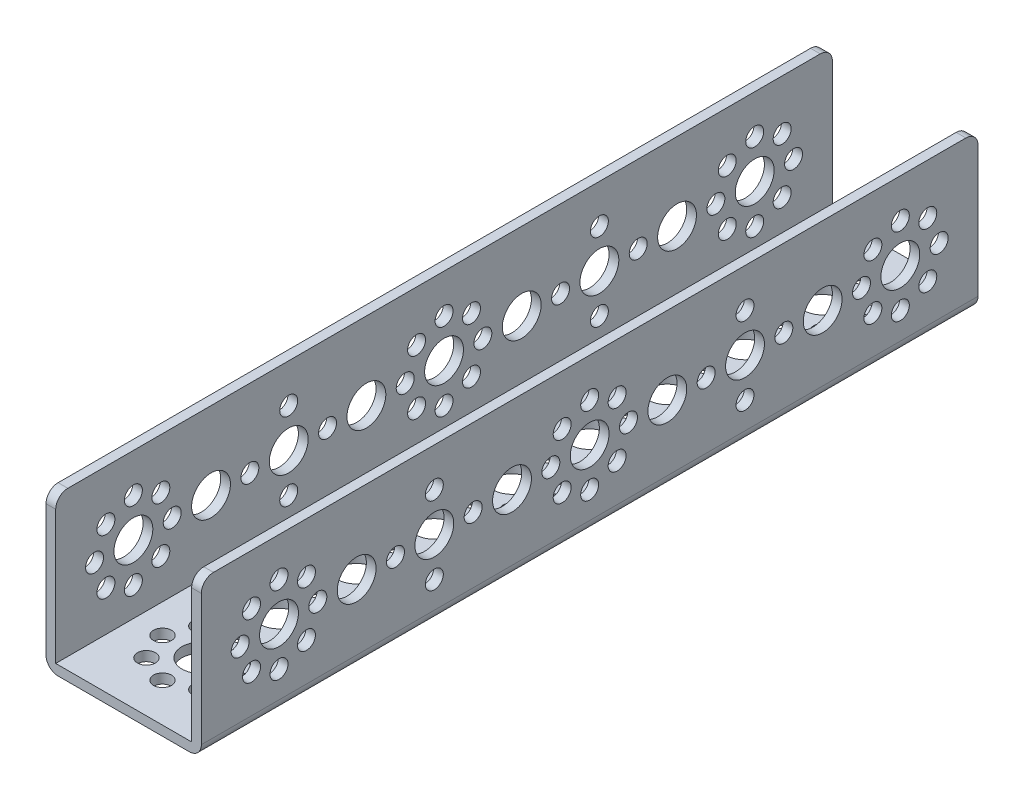
SolidWorks part; units mm, degrees
material "2024 Alloy"
ref_plane "Front Plane" through (0, 0, 0) normal (0, 0, 1) x (1, 0, 0)
ref_plane "Top Plane" through (0, 0, 0) normal (0, 1, 0) x (1, 0, 0)
ref_plane "Right Plane" through (0, 0, 0) normal (1, 0, 0) x (0, 0, -1)
ref_plane "Plane1" through (16, 0, 0) normal (1, 0, 0) x (0, 0, -1)
sketch "Sketch1" plane through (16, 0, 0) normal (1, 0, 0) x (0, 0, -1)
  line L0 (-16, 32) -> (-16, 0)
  line L1 (-16, 0) -> (144, 0)
  line L2 (144, 0) -> (144, 32)
  line L3 (144, 32) -> (-16, 32)
extrude "Boss-Extrude1" add sketch "Sketch1" against normal blind 32
sketch "Sketch2" plane through (0, 0, -144) normal (0, 0, -1) x (-1, 0, 0)
  line L0 (14, 32) -> (-14, 32)
  line L1 (-14, 32) -> (-14, 2)
  line L2 (-14, 2) -> (14, 2)
  line L3 (14, 2) -> (14, 32)
extrude "Cut-Extrude1" cut sketch "Sketch2" against normal through all
hole_wizard "Ø8.0 (8) Diameter Hole1" positions "Sketch4" profile "Sketch3" hole size "Ø8.0" standard "ANSI Metric"
sketch "Sketch4" plane through (-16, 0, 0) normal (-1, 0, 0) x (0, 0, 1)
  point P0 (-64, 16)
  point P1 (-128, 16)
  point P2 (-32, 16)
  point P3 (-96, 16)
  point P4 (-16, 16)
  point P5 (-48, 16)
  point P6 (-80, 16)
  point P7 (-112, 16)
  point P8 (0, 16)
sketch "Sketch3" plane through (-16, 16, -64) normal (0, 1, 0) x (0, 0, 1)
  line L0 (0, 0) -> (0, 2)
  line L1 (0, 2) -> (4, 2)
  line L2 (4, 2) -> (4, 0)
  line L5 (4, 0) -> (0, 0)
  line L11 (0, -6.35) -> (0, 107.95) construction
  dimension "Thru Hole Dia." = 8
  dimension "Thru Hole Depth" = 2
hole_wizard "Ø3.7 (3.7) Diameter Hole1" positions "Sketch6" profile "Sketch5" hole size "Ø3.7" standard "ANSI Metric"
sketch "Sketch6" plane through (-16, 0, 0) normal (-1, 0, 0) x (0, 0, 1)
  point P0 (0, 24)
  point P1 (0, 8)
  point P2 (-8, 16)
  point P3 (8, 16)
  point P4 (-5.6569, 21.6569)
  point P5 (5.6569, 21.6569)
  point P6 (5.6569, 10.3431)
  point P7 (-5.6569, 10.3431)
  point P8 (-64, 24)
  point P9 (-64, 8)
  point P10 (-72, 16)
  point P11 (-56, 16)
  point P12 (-69.6569, 21.6569)
  point P13 (-58.3431, 21.6569)
  point P14 (-58.3431, 10.3431)
  point P15 (-69.6569, 10.3431)
  point P16 (-128, 24)
  point P17 (-128, 8)
  point P18 (-136, 16)
  point P19 (-120, 16)
  point P20 (-133.6569, 21.6569)
  point P21 (-122.3431, 21.6569)
  point P22 (-122.3431, 10.3431)
  point P23 (-133.6569, 10.3431)
  point P24 (-32, 24)
  point P25 (-40, 16)
  point P26 (-32, 8)
  point P27 (-24, 16)
  point P28 (-96, 24)
  point P29 (-104, 16)
  point P30 (-96, 8)
  point P31 (-88, 16)
sketch "Sketch5" plane through (-16, 24, 0) normal (0, 1, 0) x (0, 0, 1)
  line L0 (0, 0) -> (0, 2)
  line L1 (0, 2) -> (1.85, 2)
  line L2 (1.85, 2) -> (1.85, 0)
  line L5 (1.85, 0) -> (0, 0)
  line L11 (0, -6.35) -> (0, 107.95) construction
  dimension "Thru Hole Dia." = 3.7
  dimension "Thru Hole Depth" = 2
hole_wizard "Ø3.7 (3.7) Diameter Hole2" positions "Sketch8" profile "Sketch7" hole size "Ø3.7" standard "ANSI Metric"
sketch "Sketch8" plane through (0, 0, 0) normal (0, -1, 0) x (-1, 0, 0)
  point P0 (8, 0)
  point P1 (5.6569, 5.6569)
  point P2 (0, 8)
  point P3 (-5.6569, 5.6569)
  point P4 (-8, 0)
  point P5 (-5.6569, -5.6569)
  point P6 (0, -8)
  point P7 (5.6569, -5.6569)
  point P8 (8, 64)
  point P9 (5.6569, 69.6569)
  point P10 (0, 72)
  point P11 (-5.6569, 69.6569)
  point P12 (-8, 64)
  point P13 (-5.6569, 58.3431)
  point P14 (0, 56)
  point P15 (5.6569, 58.3431)
  point P16 (8, 128)
  point P17 (5.6569, 133.6569)
  point P18 (0, 136)
  point P19 (-5.6569, 133.6569)
  point P20 (-8, 128)
  point P21 (-5.6569, 122.3431)
  point P22 (0, 120)
  point P23 (5.6569, 122.3431)
  point P24 (8, 32)
  point P25 (0, 40)
  point P26 (-8, 32)
  point P27 (0, 24)
  point P28 (8, 96)
  point P29 (0, 104)
  point P30 (-8, 96)
  point P31 (0, 88)
sketch "Sketch7" plane through (-8, 0, 0) normal (1, 0, 0) x (0, 0, -1)
  line L0 (0, 0) -> (0, 32)
  line L1 (0, 32) -> (1.85, 32)
  line L2 (1.85, 32) -> (1.85, 0)
  line L5 (1.85, 0) -> (0, 0)
  line L11 (0, -6.35) -> (0, 107.95) construction
  dimension "Thru Hole Dia." = 3.7
  dimension "Thru Hole Depth" = 32
hole_wizard "Ø8.0 (8) Diameter Hole2" positions "Sketch10" profile "Sketch9" hole size "Ø8.0" standard "ANSI Metric"
sketch "Sketch10" plane through (0, 0, 0) normal (0, -1, 0) x (-1, 0, 0)
  point P0 (0, 0)
  point P1 (0, 64)
  point P2 (0, 128)
  point P3 (0, 32)
  point P4 (0, 96)
  point P5 (0, 16)
  point P6 (0, 48)
  point P7 (0, 80)
  point P8 (0, 112)
sketch "Sketch9" plane through (0, 0, 0) normal (1, 0, 0) x (0, 0, -1)
  line L0 (0, 0) -> (0, 32)
  line L1 (0, 32) -> (4, 32)
  line L2 (4, 32) -> (4, 0)
  line L5 (4, 0) -> (0, 0)
  line L11 (0, -6.35) -> (0, 107.95) construction
  dimension "Thru Hole Dia." = 8
  dimension "Thru Hole Depth" = 32
hole_wizard "Ø8.0 (8) Diameter Hole3" positions "Sketch12" profile "Sketch11" hole size "Ø8.0" standard "ANSI Metric"
sketch "Sketch12" plane through (14, 0, 0) normal (-1, 0, 0) x (0, 0, 1)
  point P0 (-32, 16)
sketch "Sketch11" plane through (14, 16, -32) normal (0, 1, 0) x (0, 0, 1)
  line L0 (0, 0) -> (0, 2)
  line L1 (0, 2) -> (4, 2)
  line L2 (4, 2) -> (4, 0)
  line L5 (4, 0) -> (0, 0)
  line L11 (0, -6.35) -> (0, 107.95) construction
  dimension "Thru Hole Dia." = 8
  dimension "Thru Hole Depth" = 2
hole_wizard "Ø8.0 (8) Diameter Hole4" positions "Sketch14" profile "Sketch13" hole size "Ø8.0" standard "ANSI Metric"
sketch "Sketch14" plane through (16, 0, 0) normal (1, 0, 0) x (0, 0, -1)
  point P0 (64, 16)
  point P1 (128, 16)
  point P2 (96, 16)
  point P3 (16, 16)
  point P4 (48, 16)
  point P5 (80, 16)
  point P6 (112, 16)
  point P7 (0, 16)
sketch "Sketch13" plane through (16, 16, -64) normal (0, 1, 0) x (0, 0, -1)
  line L0 (0, 0) -> (0, 32)
  line L1 (0, 32) -> (4, 32)
  line L2 (4, 32) -> (4, 0)
  line L5 (4, 0) -> (0, 0)
  line L11 (0, -6.35) -> (0, 107.95) construction
  dimension "Thru Hole Dia." = 8
  dimension "Thru Hole Depth" = 32
hole_wizard "Ø3.7 (3.7) Diameter Hole3" positions "Sketch16" profile "Sketch15" hole size "Ø3.7" standard "ANSI Metric"
sketch "Sketch16" plane through (16, 0, 0) normal (1, 0, 0) x (0, 0, -1)
  point P0 (0, 24)
  point P1 (0, 8)
  point P2 (8, 16)
  point P3 (-8, 16)
  point P4 (5.6569, 21.6569)
  point P5 (-5.6569, 21.6569)
  point P6 (-5.6569, 10.3431)
  point P7 (5.6569, 10.3431)
  point P8 (64, 24)
  point P9 (64, 8)
  point P10 (72, 16)
  point P11 (56, 16)
  point P12 (69.6569, 21.6569)
  point P13 (58.3431, 21.6569)
  point P14 (58.3431, 10.3431)
  point P15 (69.6569, 10.3431)
  point P16 (128, 24)
  point P17 (128, 8)
  point P18 (136, 16)
  point P19 (120, 16)
  point P20 (133.6569, 21.6569)
  point P21 (122.3431, 21.6569)
  point P22 (122.3431, 10.3431)
  point P23 (133.6569, 10.3431)
  point P24 (32, 24)
  point P25 (40, 16)
  point P26 (32, 8)
  point P27 (24, 16)
  point P28 (96, 24)
  point P29 (104, 16)
  point P30 (96, 8)
  point P31 (88, 16)
sketch "Sketch15" plane through (16, 24, 0) normal (0, 1, 0) x (0, 0, -1)
  line L0 (0, 0) -> (0, 32)
  line L1 (0, 32) -> (1.85, 32)
  line L2 (1.85, 32) -> (1.85, 0)
  line L5 (1.85, 0) -> (0, 0)
  line L11 (0, -6.35) -> (0, 107.95) construction
  dimension "Thru Hole Dia." = 3.7
  dimension "Thru Hole Depth" = 32
fillet "Fillet1" radius 2.5 6 edges at (-16, 0, -64) (-15, 32, -144) (-15, 32, 16) (16, 0, -64) (15, 32, 16) (15, 32, -144) tangent propagation no
